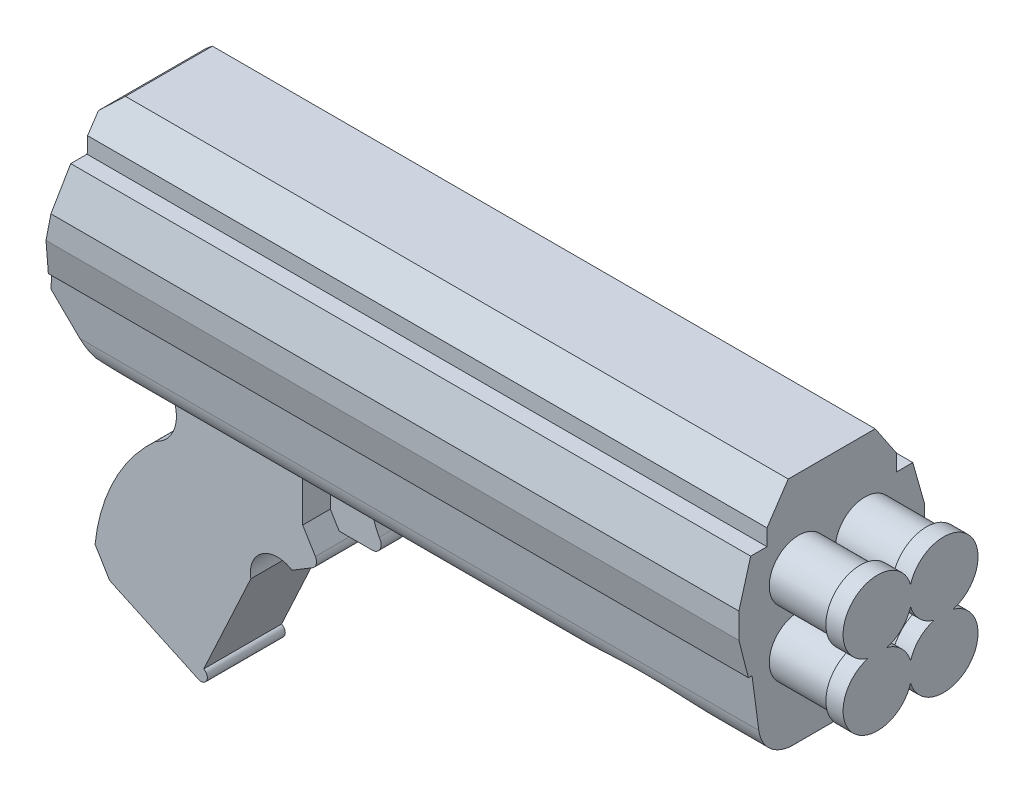
SolidWorks part; units mm, degrees
ref_plane "Front Plane" through (0, 0, 0) normal (0, 0, 1) x (1, 0, 0)
ref_plane "Top Plane" through (0, 0, 0) normal (0, 1, 0) x (1, 0, 0)
ref_plane "Right Plane" through (0, 0, 0) normal (1, 0, 0) x (0, 0, -1)
sketch "Sketch2" plane through (0, 0, 0) normal (0, 0, 1) x (1, 0, 0)
  line L11 (-190.5, -12.7) -> (-190.5, -4.318)
  line L12 (-190.5, -4.318) -> (-185.8441, 0)
  line L13 (-185.8441, 0) -> (0, 0)
  line L14 (0, 0) -> (0, -65.278)
  line L15 (-87.376, -67.818) -> (-87.376, -62.23)
  line L16 (-87.376, -62.23) -> (-137.414, -62.23)
  line L22 (-133.865, -86.3863) -> (-137.414, -80.518)
  line L23 (-137.414, -80.518) -> (-137.414, -62.23)
  line L24 (-195.6384, -114.312) -> (-191.5636, -121.0496)
  line L26 (-190.5, -12.7) -> (-197.2741, -47.752)
  line L27 (-197.2741, -47.752) -> (-187.3681, -60.9537)
  line L28 (-187.3681, -60.9537) -> (-180.7641, -62.23)
  line L29 (-191.5636, -121.0496) -> (-166.6762, -132.588)
  line L30 (-179.1199, -126.8188) -> (-157.9789, -81.2195) construction
  line L31 (-165.1805, -129.3619) -> (-151.961, -100.8485)
  line L32 (-140.4108, -92.9902) -> (-134.6304, -89.4943)
  line L33 (-166.6762, -132.588) -> (-151.961, -100.8485) construction
  line L34 (-137.414, -62.23) -> (-180.7641, -62.23) construction
  line L35 (-195.6384, -114.312) -> (-182.5406, -86.0612) construction
  arc A3 (-58.2313, -64.516) -> (-87.376, -67.818) centre (-79.9963, -2.6819) cw
  arc A13 (0, -65.278) -> (-3.6213, -65.95) centre (-2.2236, -63.3886) cw
  arc A14 (-3.6213, -65.95) -> (-58.2313, -64.516) centre (-32.8043, -136.7537) ccw
  arc A16 (-134.6304, -89.4943) -> (-133.865, -86.3863) centre (-135.8017, -87.5576) ccw
  arc A17 (-180.7641, -62.23) -> (-178.6204, -80.7926) centre (-182.6232, -71.8498) cw
  arc A24 (-195.6384, -114.312) -> (-178.6204, -80.7926) centre (-143.1032, -119.9047) cw
  arc A25 (-166.6762, -132.588) -> (-165.1805, -129.3619) centre (-165.9284, -130.9749) ccw
  arc A27 (-140.4108, -92.9902) -> (-151.961, -100.8485) centre (-144.4729, -99.4372) ccw
  point P0 (-30.7941, -60.198)
  point P1 (-172.8901, -70.7258)
  point P10 (-133.604, -88.0988)
  point P37 (-72.6166, -67.818)
  point P55 (-185.0889, -87.8357)
  dimension "D34" = 7.62
  dimension "D13" = 67.31
  dimension "D26" = 52.832
  dimension "D31" = 1.778
  dimension "D3" = 65.278
  dimension "D4" = 62.23
  dimension "D5" = 87.376
  dimension "D6" = 24.384
  dimension "D7" = 6.604
  dimension "D8" = 37.592
  dimension "D9" = 9.398
  dimension "D10" = 137.414
  dimension "D11" = 190.5
  dimension "D12" = 18.288
  dimension "D14" = 8.382
  dimension "D15" = 6.35
  dimension "D16" = 4.318
  dimension "D17" = 11.43
  dimension "D18" = 12.7
  dimension "D19" = 3.6213
  dimension "D20" = 54.61
  dimension "D21" = 5.588
  dimension "D22" = 3.302
  dimension "D23" = 14.478
  dimension "D24" = 7.62
  dimension "D25" = 16.51
  dimension "D27" = 27.432
  dimension "D28" = 7.874
  dimension "D29" = 70.358
  dimension "D30" = 13.97
  dimension "D32" = 6.858
  dimension "D33" = 3.81
  dimension "D39" = 17.018
extrude "Boss-Extrude1" add sketch "Sketch2" along normal mid plane 52.07
sketch "Sketch4" plane through (0, 0, 0) normal (1, 0, 0) x (0, 0, -1)
  line L0 (0, 0) -> (0, -65.278) construction
  line L1 (-26.035, 0) -> (26.035, 0) construction
  line L2 (-26.035, -65.278) -> (26.035, -65.278) construction
  line L3 (-12.192, 0) -> (12.192, 0)
  line L4 (12.192, 0) -> (18.161, -8.89)
  line L5 (18.161, -8.89) -> (18.161, -13.462)
  line L6 (18.161, -13.462) -> (22.733, -13.462)
  line L8 (-26.035, -32.258) -> (-26.035, -25.146)
  line L10 (23.368, -42.672) -> (22.352, -42.672)
  line L11 (22.352, -42.672) -> (20.447, -56.9402)
  line L13 (0, 0) -> (0, -65.278)
  line L14 (23.368, -42.672) -> (26.035, -32.258)
  line L15 (26.035, -65.278) -> (26.035, 0) construction
  line L16 (26.035, -32.258) -> (26.035, -25.146)
  line L17 (26.035, -25.146) -> (22.733, -13.462)
  line L18 (-23.368, -42.672) -> (-26.035, -32.258)
  line L19 (-23.368, -42.672) -> (-22.352, -42.672)
  line L20 (-22.352, -42.672) -> (-20.447, -56.9402)
  line L21 (-12.192, 0) -> (-18.161, -8.89)
  line L22 (-18.161, -8.89) -> (-18.161, -13.462)
  line L23 (-18.161, -13.462) -> (-22.733, -13.462)
  line L24 (-26.035, -25.146) -> (-22.733, -13.462)
  line L25 (-12.192, 0) -> (-26.035, 0)
  line L26 (-26.035, 0) -> (-26.035, -25.146)
  line L27 (-26.035, -132.7529) -> (-26.035, -32.258)
  line L28 (-10.922, -65.278) -> (-10.922, -132.7529)
  line L29 (-26.035, -132.7529) -> (26.035, -132.7529) construction
  line L30 (26.035, -132.7529) -> (26.035, -32.258)
  line L31 (26.035, -25.146) -> (26.035, 0)
  line L32 (26.035, 0) -> (12.192, 0)
  line L33 (-10.922, -132.7529) -> (-26.035, -132.7529)
  line L34 (26.035, -132.7529) -> (10.922, -132.7529)
  line L35 (10.922, -132.7529) -> (10.922, -65.278)
  arc A0 (20.447, -56.9402) -> (10.922, -65.278) centre (10.922, -55.6685) cw
  arc A1 (-20.447, -56.9402) -> (-10.922, -65.278) centre (-10.922, -55.6685) ccw
  line M15 (26.035, -65.278) -> (26.035, 0)
  line M16 (26.035, 0) -> (-26.035, 0)
  line M17 (-26.035, 0) -> (-26.035, -65.278)
  line M18 (-26.035, -65.278) -> (26.035, -65.278)
  dimension "D10" = 1.016
  dimension "D14" = 9.6095
  dimension "D1" = 12.192
  dimension "D2" = 18.161
  dimension "D3" = 8.89
  dimension "D4" = 29.21
  dimension "D5" = 11.684
  dimension "D6" = 4.572
  dimension "D7" = 4.572
  dimension "D8" = 7.112
  dimension "D9" = 22.352
  dimension "D11" = 10.922
  dimension "D12" = 5.588
  dimension "D13" = 21.844
extrude "Cut-Extrude2" cut sketch "Sketch4" against normal through all contours A1 L20 L19 L18 M17 M18 | L24 L23 L22 L21 M17 M16 | L17 L4 L5 L6 M15 M16 | L11 A0 L14 L10 M18 M15 | L18 L19 L20 A1 L28 L33 L27 | L30 L34 L35 A0 L11 L10 L14 region at (0, -7.4226, 21.4226) region at (0, -7.4226, -21.4226) region at (0, -54.3878, 22.9775) region at (0, -54.3878, -22.9775)
sketch "Sketch5" plane through (0, 0, 0) normal (1, 0, 0) x (0, 0, -1)
  line L0 (0, 0) -> (0, -65.278) construction
  line L1 (-12.192, 0) -> (12.192, 0) construction
  line L2 (-10.922, -65.278) -> (10.922, -65.278) construction
  line L3 (-32.3725, -32.639) -> (32.3725, -32.639) construction
  line L4 (-17.526, -23.368) -> (17.526, -23.368) construction
  line L5 (9.271, -15.113) -> (9.271, -50.165) construction
  circle A0 centre (-9.271, -23.368) radius 8.255
  circle A1 centre (9.271, -23.368) radius 8.255
  circle A2 centre (9.271, -41.91) radius 8.255
  circle A3 centre (-9.271, -41.91) radius 8.255
  point P10 (0, -32.639)
  point P16 (0, -23.368)
  point P20 (9.271, -32.639)
  dimension "D1" = 16.51
  dimension "D3" = 16.51
  dimension "D4" = 16.51
  dimension "D2" = 35.052
  dimension "D5" = 35.052
extrude "Boss-Extrude8" add sketch "Sketch5" along normal blind 17.272
sketch "Sketch6" plane through (17.272, 0, 0) normal (1, 0, 0) x (0, 0, -1)
  line L0 (0, 0) -> (0, -65.278) construction
  line L1 (-10.922, -65.278) -> (10.922, -65.278) construction
  line L2 (53.7544, -32.639) -> (-43.1333, -32.639) construction
  arc A0 (0, -20.6829) -> (-11.9561, -32.639) centre (-9.271, -23.368) ccw
  arc A1 (0, -20.6829) -> (11.9561, -32.639) centre (9.271, -23.368) cw
  arc A2 (0, -44.5951) -> (11.9561, -32.639) centre (9.271, -41.91) ccw
  arc A3 (-6.5859, -32.639) -> (0, -39.2249) centre (-9.271, -41.91) cw
  arc A4 (-6.5859, -32.639) -> (0, -26.0531) centre (-9.271, -23.368) ccw
  arc A5 (0, -44.5951) -> (-11.9561, -32.639) centre (-9.271, -41.91) cw
  arc A6 (6.5859, -32.639) -> (0, -39.2249) centre (9.271, -41.91) ccw
  arc A7 (6.5859, -32.639) -> (0, -26.0531) centre (9.271, -23.368) cw
  point P10 (0, -32.639)
  dimension "D1" = 19.304
extrude "Boss-Extrude11" add sketch "Sketch6" along normal blind 4.826
sketch "Sketch8" plane through (0, 0, 0) normal (0, 0, 1) x (1, 0, 0)
  line L0 (-134.9282, -84.6282) -> (-125.7166, -84.6282)
  line L2 (-137.414, -62.23) -> (-87.376, -62.23) construction
  line L3 (-137.414, -80.518) -> (-137.414, -65.278) construction
  line L4 (-123.19, -62.23) -> (-137.414, -62.23)
  line L5 (-137.414, -62.23) -> (-137.414, -80.518)
  line L6 (-137.414, -80.518) -> (-134.9282, -84.6282)
  line L9 (-133.865, -86.3863) -> (-137.414, -80.518) construction
  line L10 (-140.4108, -92.9902) -> (-134.6304, -89.4943) construction
  arc A0 (-125.7166, -84.6282) -> (-123.6867, -80.5614) centre (-125.7166, -82.0882) ccw
  arc A1 (-123.6867, -80.5614) -> (-123.19, -62.23) centre (-108.2105, -71.8083) cw
  arc A2 (-134.6304, -89.4943) -> (-133.865, -86.3863) centre (-135.8017, -87.5576) ccw construction
  point P2 (-132.1895, -84.4662)
  point P3 (0, 0)
  point P10 (-123.5629, -80.518)
  point P11 (-125.984, -71.3267)
  point P22 (0, 0)
  point P23 (-124.9672, -81.8667)
  point P27 (-133.604, -88.0988)
  point P28 (-123.444, -83.2226)
  dimension "D5" = 2.54
  dimension "D6" = 17.78
  dimension "D1" = 11.43
  dimension "D2" = 4.318
  dimension "D3" = 14.224
  dimension "D4" = 10.16
extrude "Boss-Extrude12" add sketch "Sketch8" along normal mid plane 6.35
